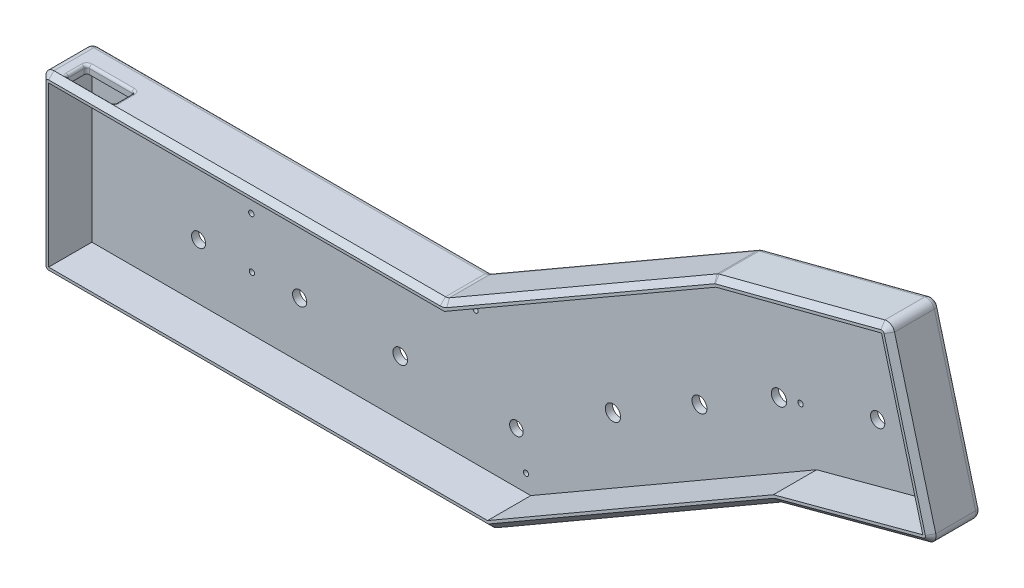
SolidWorks part; units mm, degrees
ref_plane "Plan de face" through (0, 0, 0) normal (0, 0, 1) x (1, 0, 0)
ref_plane "Plan de dessus" through (0, 0, 0) normal (0, 1, 0) x (1, 0, 0)
ref_plane "Plan de droite" through (0, 0, 0) normal (1, 0, 0) x (0, 0, -1)
sketch "Model" plane through (0, 0, 0) normal (0, 0, 1) x (1, 0, 0)
  line L0 (152.8114, 25.9717) -> (138.2826, 80.2215) construction
  line L1 (98.1506, 11.3316) -> (152.8114, 25.9717) construction
  line L2 (-9.3986, -50.8585) -> (98.1506, 11.3316) construction
  line L3 (-172.3739, -50.8585) -> (-9.3986, -50.8585) construction
  line L4 (-24.5886, 5.3017) -> (-172.3739, 5.2915) construction
  line L5 (138.2826, 80.2215) -> (78.0109, 64.5416) construction
  line L6 (-151.6088, 5.3124) -> (-151.6088, 5.2929)
  line L7 (-24.5886, 5.3017) -> (78.0109, 64.5416) construction
  line L8 (-172.3739, 5.2915) -> (-172.3739, -50.6876) construction
  line L9 (-172.3739, -50.6876) -> (-172.3739, -50.8585) construction
  line L10 (-25.1245, 7.3016) -> (-174.3739, 7.2914)
  line L11 (-174.3739, 7.2914) -> (-174.3739, -50.6876)
  line L12 (-174.3739, -50.6876) -> (-174.3739, -52.8585)
  line L13 (-174.3739, -52.8585) -> (-8.862, -52.8585)
  line L14 (-8.862, -52.8585) -> (98.9231, 9.4681)
  line L15 (98.9231, 9.4681) -> (155.2607, 24.5572)
  line L16 (155.2607, 24.5572) -> (139.7008, 82.657)
  line L17 (139.7008, 82.657) -> (77.2454, 66.409)
  line L18 (-25.1245, 7.3016) -> (77.2454, 66.409)
  line L19 (-25.9285, 10.3016) -> (-177.3739, 10.2912)
  line L20 (-177.3739, 10.2912) -> (-177.3739, -50.6876)
  line L21 (-177.3739, -50.6876) -> (-177.3739, -55.8585)
  line L22 (-177.3739, -55.8585) -> (-8.057, -55.8585)
  line L23 (-8.057, -55.8585) -> (100.0819, 6.6727)
  line L24 (100.0819, 6.6727) -> (158.9346, 22.4355)
  line L25 (158.9346, 22.4355) -> (141.8281, 86.3103)
  line L26 (141.8281, 86.3103) -> (76.097, 69.2101)
  line L27 (-25.9285, 10.3016) -> (76.097, 69.2101)
  circle A0 centre (80.6856, 58.4893) radius 1
  circle A1 centre (92.8776, 28.0855) radius 1
  circle A2 centre (-29.7028, -2.6485) radius 1
  circle A3 centre (-10.6528, -46.4381) radius 1
  circle A4 centre (-114.2594, -13.4181) radius 1
  circle A5 centre (-114.0308, -32.4935) radius 1
  dimension "D1" = 2
  dimension "D2" = 3
extrude "Boss.-Extru.1" add sketch "Model" along normal blind 19 contours L27 L19 L20 L21 L22 L23 L24 L25 L26 L10 L18 L17 L16 L15 L14 L13 L12 L11 region at (25.2668, 39.4396, 0)
fillet "Congé1" radius 3 8 edges at (-25.9285, 10.3016, 9.5) (76.097, 69.2101, 9.5) (141.8281, 86.3103, 9.5) (158.9346, 22.4355, 9.5) (100.0819, 6.6727, 9.5) (-8.057, -55.8585, 9.5) (-177.3739, -55.8585, 9.5) (-177.3739, 10.2912, 9.5)
sketch "Esquisse1" plane through (0, 0, 0) normal (0, 0, 1) x (1, 0, 0)
  line L0 (-25.1245, 7.3016) -> (-174.3739, 7.2914) construction
  line L1 (-25.1245, 7.3016) -> (77.2454, 66.409) construction
  line L2 (139.7008, 82.657) -> (77.2454, 66.409) construction
  line L3 (155.2607, 24.5572) -> (139.7008, 82.657) construction
  line L4 (98.9231, 9.4681) -> (155.2607, 24.5572) construction
  line L5 (-8.862, -52.8585) -> (98.9231, 9.4681) construction
  line L6 (-174.3739, -52.8585) -> (-8.862, -52.8585) construction
  line L7 (-174.3739, -50.6876) -> (-174.3739, -52.8585) construction
  line L8 (-174.3739, 7.2914) -> (-174.3739, -50.6876) construction
  line L9 (-25.1245, 7.3016) -> (-174.3739, 7.2914)
  line L10 (-25.1245, 7.3016) -> (77.2454, 66.409)
  line L11 (139.7008, 82.657) -> (77.2454, 66.409)
  line L12 (155.2607, 24.5572) -> (139.7008, 82.657)
  line L13 (98.9231, 9.4681) -> (155.2607, 24.5572)
  line L14 (-8.862, -52.8585) -> (98.9231, 9.4681)
  line L15 (-174.3739, -52.8585) -> (-8.862, -52.8585)
  line L16 (-174.3739, -50.6876) -> (-174.3739, -52.8585)
  line L17 (-174.3739, 7.2914) -> (-174.3739, -50.6876)
  circle A0 centre (-114.2594, -13.4181) radius 1 construction
  circle A1 centre (-114.2594, -13.4181) radius 1
  circle A2 centre (-114.0308, -32.4935) radius 1 construction
  circle A3 centre (-114.0308, -32.4935) radius 1
  circle A4 centre (-29.7028, -2.6485) radius 1 construction
  circle A5 centre (-29.7028, -2.6485) radius 1
  circle A6 centre (-10.6528, -46.4381) radius 1 construction
  circle A7 centre (-10.6528, -46.4381) radius 1
  circle A8 centre (80.6856, 58.4893) radius 1 construction
  circle A9 centre (80.6856, 58.4893) radius 1
  circle A10 centre (92.8776, 28.0855) radius 1 construction
  circle A11 centre (92.8776, 28.0855) radius 1
extrude "Boss.-Extru.2" add sketch "Esquisse1" along normal blind 2.7
sketch "Esquisse2" plane through (0, 0, 0) normal (0, 0, -1) x (-1, 0, 0)
  circle A0 centre (-80.6856, 58.4893) radius 1 construction
  circle A1 centre (-92.8776, 28.0855) radius 1 construction
  circle A2 centre (29.7028, -2.6485) radius 1 construction
  circle A3 centre (10.6528, -46.4381) radius 1 construction
  circle A4 centre (114.2594, -13.4181) radius 1 construction
  circle A5 centre (114.0308, -32.4935) radius 1 construction
  circle A6 centre (-80.6856, 58.4893) radius 1
  circle A7 centre (-92.8776, 28.0855) radius 1
  circle A8 centre (29.7028, -2.6485) radius 1
  circle A9 centre (10.6528, -46.4381) radius 1
  circle A10 centre (114.2594, -13.4181) radius 1
  circle A11 centre (114.0308, -32.4935) radius 1
  circle A12 centre (-80.6856, 58.4893) radius 2
  circle A13 centre (-92.8776, 28.0855) radius 2
  circle A14 centre (29.7028, -2.6485) radius 2
  circle A15 centre (10.6528, -46.4381) radius 2
  circle A16 centre (114.2594, -13.4181) radius 2
  circle A17 centre (114.0308, -32.4935) radius 2
  dimension "D1" = 1
extrude "Enlèv. mat.-Extru.1" cut sketch "Esquisse2" against normal blind 1
chamfer "Chanfrein1" distance 2 angle 45 16 edges at (141.2104, 85.2495, 19) (150.3786, 54.3832, 19) (157.8586, 23.0569, 19) (128.2507, 14.2173, 19) (100.0919, 6.6486, 19) (46.1894, -24.4906, 19) (-8.0845, -55.756, 19) (-91.6179, -55.8585, 19) (-176.4952, -54.9798, 19) (-177.3739, -22.7836, 19) (-176.4953, 9.4126, 19) (-100.5532, 10.2965, 19) (-25.9559, 10.4038, 19) (25.2564, 39.8553, 19) (76.1074, 69.1848, 19) (107.7178, 77.4364, 19)
fillet "Congé2" radius 2 16 edges at (100.0919, 6.6486, 0) (46.1894, -24.4906, 0) (-8.0845, -55.756, 0) (-91.6179, -55.8585, 0) (-176.4952, -54.9798, 0) (-177.3739, -22.7836, 0) (-176.4953, 9.4126, 0) (-100.5532, 10.2965, 0) (-25.9559, 10.4038, 0) (25.2564, 39.8553, 0) (76.1074, 69.1848, 0) (107.7178, 77.4364, 0) (141.2104, 85.2495, 0) (150.3786, 54.3832, 0) (157.8586, 23.0569, 0) (128.2507, 14.2173, 0)
sketch "Esquisse3" plane through (-0.0007, 10.3034, 0) normal (-0.0001, 1, 0) x (1, 0.0001, 0)
  line L0 (-174.3734, -2) -> (-174.3734, -17) construction
  line L1 (-169.3734, -8.6) -> (-153.3734, -8.6)
  line L2 (-170.3734, -9.6) -> (-170.3734, -15.5)
  line L3 (-169.3734, -16.5) -> (-153.3734, -16.5)
  line L4 (-152.3734, -9.6) -> (-152.3734, -15.5)
  line L6 (-174.3734, 0) -> (-26.7316, 0) construction
  line L7 (-26.7316, -19) -> (-174.3734, -19) construction
  arc A0 (-170.3734, -15.5) -> (-169.3734, -16.5) centre (-169.3734, -15.5) ccw
  arc A1 (-153.3734, -16.5) -> (-152.3734, -15.5) centre (-153.3734, -15.5) ccw
  arc A2 (-153.3734, -8.6) -> (-152.3734, -9.6) centre (-153.3734, -9.6) cw
  arc A3 (-169.3734, -8.6) -> (-170.3734, -9.6) centre (-169.3734, -9.6) ccw
  point P10 (-170.3734, -16.5)
  point P13 (-152.3734, -16.5)
  point P16 (-152.3734, -8.6)
  dimension "D5" = 1
  dimension "D1" = 4
  dimension "D2" = 18
  dimension "D3" = 2.5
  dimension "D4" = 8.6
extrude "Enlèv. mat.-Extru.2" cut sketch "Esquisse3" against normal blind 10
fillet "Congé3" radius 1 8 edges at (-152.667, 10.2929, 8.8929) (-152.3741, 10.2929, 12.55) (-152.667, 10.2929, 16.2071) (-161.3741, 10.2923, 16.5) (-170.0812, 10.2917, 16.2071) (-170.3741, 10.2917, 12.55) (-170.0812, 10.2917, 8.8929) (-161.3741, 10.2923, 8.6)
sketch "Esquisse4" plane through (0, 0, 0) normal (0, 0, 1) x (1, 0, 0)
  circle A0 centre (-134.1394, -31.928) radius 2.6575
  circle A1 centre (-96.0262, -31.928) radius 2.6813
  circle A2 centre (-58.1085, -31.928) radius 2.7625
  circle A3 centre (-14.2866, -33.5542) radius 2.56
  circle A4 centre (22.1119, -10.2814) radius 2.8929
  circle A5 centre (54.7478, 8.6934) radius 2.8222
  circle A6 centre (84.7109, 25.9763) radius 2.8889
  circle A7 centre (121.9376, 37.3583) radius 2.6958
extrude "Enlèv. mat.-Extru.4" cut sketch "Esquisse4" along normal blind 10
